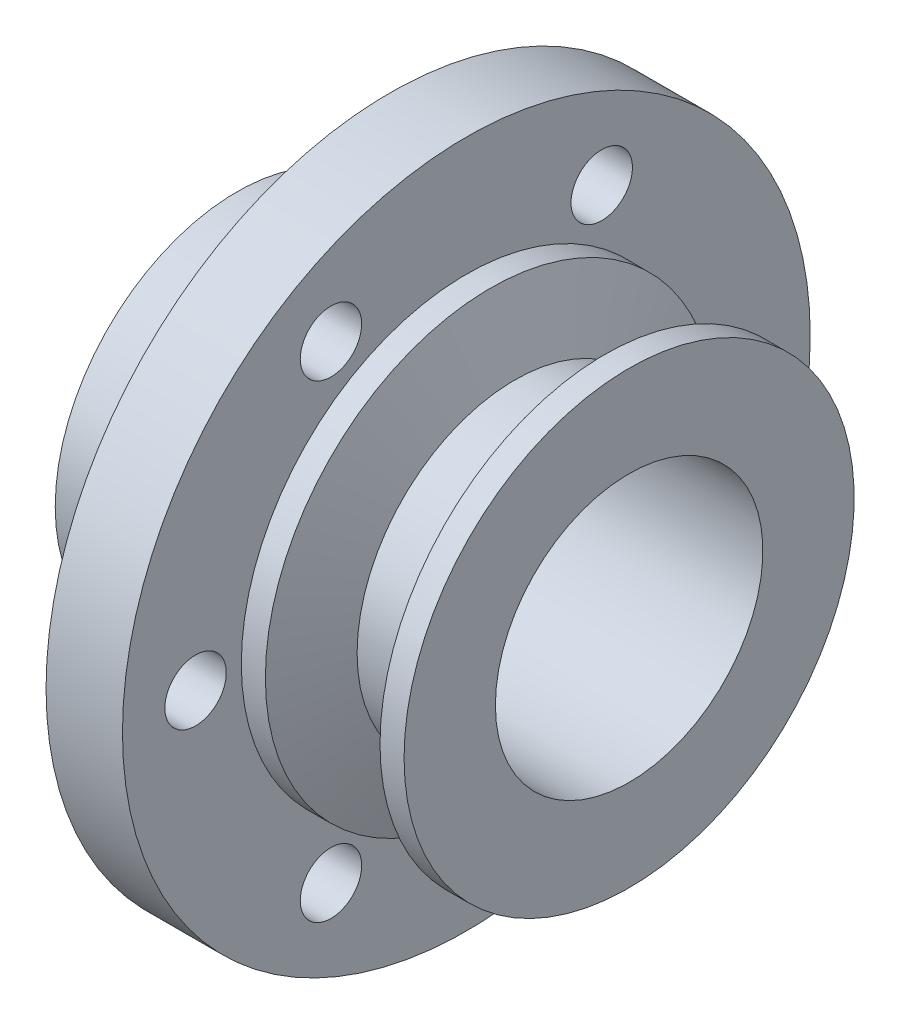
SolidWorks part; units mm, degrees
ref_plane "Front" through (0, 0, 0) normal (0, 0, 1) x (1, 0, 0)
ref_plane "Top" through (0, 0, 0) normal (0, 1, 0) x (1, 0, 0)
ref_plane "Right" through (0, 0, 0) normal (1, 0, 0) x (0, 0, -1)
sketch "Sketch1" plane through (0, 0, 0) normal (0, 0, 1) x (1, 0, 0)
  line L0 (-12.7, 15.1125) -> (0, 15.1125)
  line L1 (0, 15.1125) -> (0, 28.575)
  line L2 (0, 28.575) -> (6.35, 28.575)
  line L3 (6.35, 28.575) -> (6.35, 18.7005)
  line L4 (6.35, 18.7005) -> (8.35, 18.7005)
  line L5 (8.35, 18.7005) -> (10.3839, 13.1125)
  line L6 (10.3839, 13.1125) -> (15.8411, 13.1125)
  line L7 (15.8411, 13.1125) -> (17.875, 18.7005)
  line L8 (17.875, 18.7005) -> (19.875, 18.7005)
  line L9 (19.875, 18.7005) -> (19.875, 11.1125)
  line L10 (0, 0) -> (27.6559, 0) construction
  line L12 (19.875, 11.1125) -> (4, 11.1125)
  line L13 (4, 11.1125) -> (4, 8.9375)
  line L14 (4, 8.9375) -> (1.5875, 8.9375)
  line L15 (1.5875, 8.9375) -> (1.5875, 11.1125)
  line L16 (1.5875, 11.1125) -> (-12.7, 11.1125)
  line L17 (-12.7, 11.1125) -> (-12.7, 15.1125)
  line L18 (13.1125, 13.1125) -> (13.1125, 25.8182) construction
  dimension "D1" = 9.525
  dimension "D3" = 30.225
  dimension "D4" = 22.225
  dimension "D5" = 5.588
  dimension "D7" = 2
  dimension "D8" = 40
  dimension "D9" = 14.2875
  dimension "D10" = 15.875
  dimension "D11" = 2
  dimension "D12" = 2
  dimension "D13" = 6.35
  dimension "D14" = 17.875
  dimension "D15" = 12.7
  dimension "D16" = 57.15
revolve "Revolve1" add sketch "Sketch1" angle 360 about L10
hole_wizard "1/4-20 Tapped Hole1" positions "Sketch2" profile "Sketch4" tap size "1/4-20" standard "ANSI Inch"
sketch "Sketch2" plane through (0, 0, 0) normal (-1, 0, 0) x (0, 0, 1)
  circle A0 centre (0, 0) radius 22.5 construction
  point P16 (-22.5, 0)
  point P24 (-11.25, 19.4856)
  point P25 (11.25, 19.4856)
  point P26 (22.5, 0)
  point P27 (11.25, -19.4856)
  point P28 (-11.25, -19.4856)
  dimension "D1" = 45
  dimension "D2" = 6
sketch "Sketch4" plane through (0, -19.4856, -11.25) normal (0, 1, 0) x (0, 0, 1)
  line L0 (0, 0) -> (0, 18.0438)
  line L1 (0, 18.0438) -> (2.5527, 16.51)
  line L2 (2.5527, 16.51) -> (2.5527, 0)
  line L5 (2.5527, 0) -> (0, 0)
  line L10 (0, 18.0438) -> (-2.5527, 16.51) construction
  line L11 (0, -6.35) -> (0, 107.95) construction
  dimension "Tap Drill Dia." = 5.1054
  dimension "Tap Drill Depth" = 16.51
  dimension "Drill Angle" = 118
cosmetic thread "Hole Thread1"
cosmetic thread "Hole Thread2"
cosmetic thread "Hole Thread3"
cosmetic thread "Hole Thread4"
cosmetic thread "Hole Thread7"
cosmetic thread "Hole Thread8"
